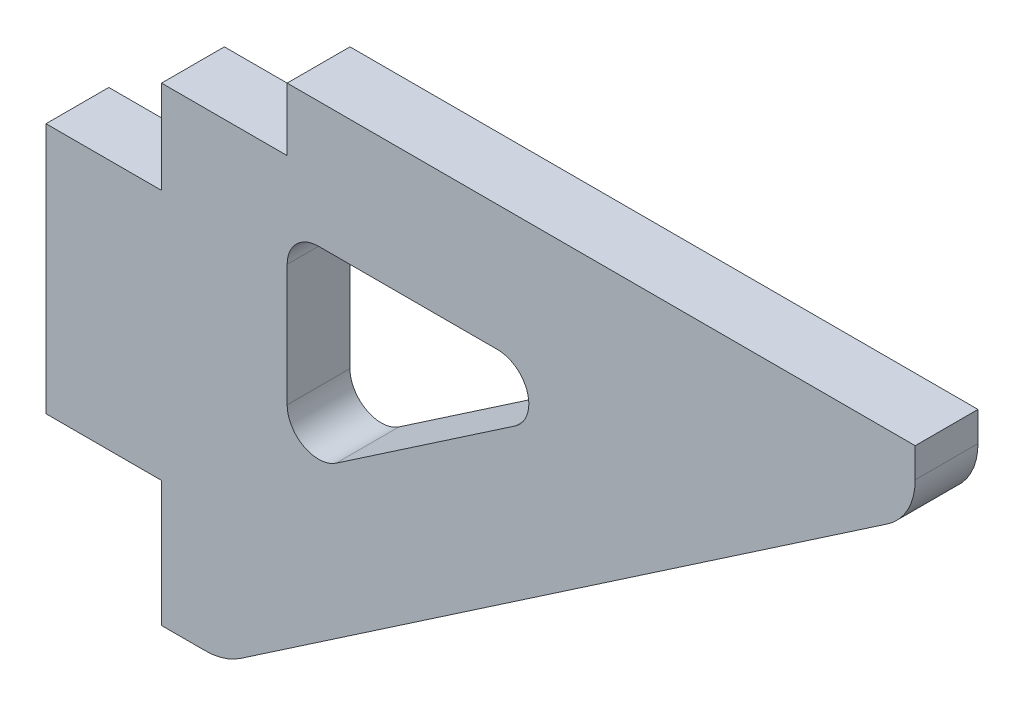
SolidWorks part; units mm, degrees
ref_plane "Front Plane" through (0, 0, 0) normal (0, 0, 1) x (1, 0, 0)
ref_plane "Top Plane" through (0, 0, 0) normal (0, 1, 0) x (1, 0, 0)
ref_plane "Right Plane" through (0, 0, 0) normal (1, 0, 0) x (0, 0, -1)
sketch "Sketch1" plane through (0, 0, 0) normal (0, 0, 1) x (1, 0, 0)
  line L0 (2.921, 6.35) -> (2.921, 11.049)
  line L1 (2.921, -6.35) -> (-2.921, -6.35)
  line L2 (6.096, -12.7) -> (41.021, 11.049)
  line L3 (2.921, 6.35) -> (-2.921, 6.35)
  line L4 (-2.921, -6.35) -> (-2.921, 6.35)
  line L5 (2.921, -6.35) -> (-2.921, 6.35) construction
  line L6 (2.921, 6.35) -> (-2.921, -6.35) construction
  line L7 (9.271, 14.224) -> (41.021, 14.224)
  line L8 (41.021, 14.224) -> (41.021, 11.049)
  line L9 (2.921, -6.35) -> (2.921, -12.7)
  line L10 (2.921, -12.7) -> (6.096, -12.7)
  line L11 (2.921, 14.224) -> (20.8815, -3.7365) construction
  line L12 (9.271, -2.862) -> (25.0592, 7.874)
  line L13 (9.271, -2.862) -> (9.271, 7.874)
  line L14 (9.271, 7.874) -> (25.0592, 7.874)
  line L16 (2.921, 11.049) -> (9.271, 11.049)
  line L17 (9.271, 14.224) -> (9.271, 11.049)
  point P0 (0, 0)
  dimension "D1" = 12.7
  dimension "D2" = 5.842
  dimension "D3" = 14.224
  dimension "D4" = 38.1
  dimension "D5" = 3.175
  dimension "D6" = 6.35
  dimension "D7" = 3.175
  dimension "D8" = 45
  dimension "D9" = 25.4
  dimension "D10" = 3.175
  dimension "D11" = 6.35
  dimension "D12" = 6.35
  dimension "D13" = 6.35
  dimension "D14" = 3.175
extrude "Boss-Extrude1" add sketch "Sketch1" along normal blind 3.175
fillet "Fillet1" radius 1.5875 3 edges at (25.0592, 7.874, 1.5875) (9.271, 7.874, 1.5875) (9.271, -2.862, 1.5875)
fillet "Fillet2" radius 3.175 2 edges at (6.096, -12.7, 1.5875) (41.021, 11.049, 1.5875)
